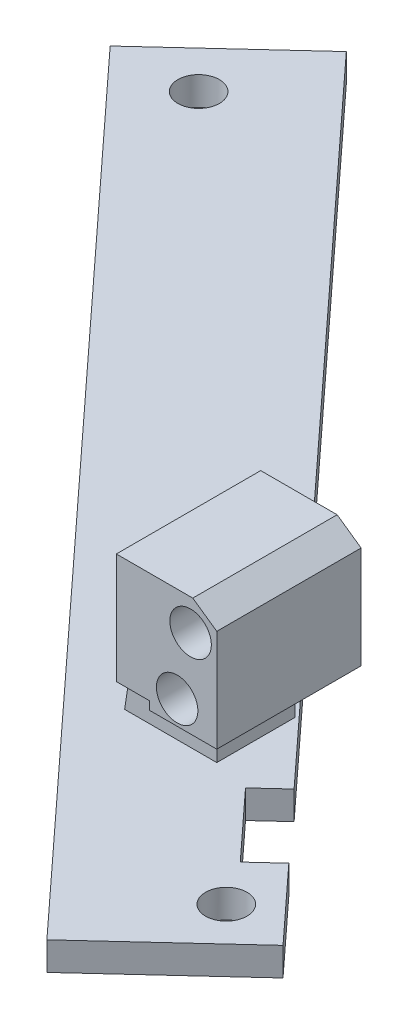
SolidWorks part; units mm, degrees
ref_plane "Front Plane" through (0, 0, 0) normal (0, 0, 1) x (1, 0, 0)
ref_plane "Top Plane" through (0, 0, 0) normal (0, 1, 0) x (1, 0, 0)
ref_plane "Right Plane" through (0, 0, 0) normal (1, 0, 0) x (0, 0, -1)
sketch "Sketch1" plane through (0, 0, 0) normal (0, 0, 1) x (1, 0, 0)
  line L0 (-629.0113, 228.5148) -> (-646.4173, 232.1744)
  line L1 (-625.5069, 227.7779) -> (-640.2031, 230.8679) construction
  line L2 (-646.4173, 232.1744) -> (-650.3578, 213.4325)
  line L3 (-650.3578, 213.4325) -> (-632.9518, 209.7729)
  line L4 (-626.0822, 208.3286) -> (-644.038, 212.1038) construction
  line L6 (-629.0113, 228.5148) -> (-629.0113, 209.7729)
  line L7 (-629.0113, 209.7729) -> (-632.9518, 209.7729)
  circle A0 centre (-635.0536, 225) radius 3.175
  circle A1 centre (-637.1112, 215.214) radius 3.175
  dimension "D4" = 6.35
  dimension "D5" = 6.35
  dimension "D1" = 6.35
  dimension "D2" = 19.1516
  dimension "D3" = 18.7418
  dimension "D6" = 21.3464
extrude "Boss-Extrude1" add sketch "Sketch1" along normal up to surface (22.098 mm away)
sketch "Sketch2" plane through (15.4424, 73.4471, 0) normal (-0.2058, -0.9786, 0) x (0.9786, -0.2058, 0)
  line L0 (-680.3571, 22.098) -> (-680.3571, 0)
  line L1 (-680.3571, 0) -> (-673.9925, 0)
  line L2 (-680.3571, 0) -> (-662.5706, 0) construction
  line L3 (-673.9925, 0) -> (-673.9925, 22.098)
  line L4 (-662.5706, 22.098) -> (-680.3571, 22.098) construction
  line L5 (-673.9925, 22.098) -> (-680.3571, 22.098)
  dimension "D1" = 6.3646
extrude "Boss-Extrude2" add sketch "Sketch2" along normal blind 8.89 contours L5 L0 L1 L3
ref_plane "Plane5" through (0, 204.7328, 0) normal (0, 1, 0) x (1, 0, 0)
sketch "Sketch12" plane through (0, 204.7328, 0) normal (0, 1, 0) x (1, 0, 0)
  line L11 (-739.2843, 69.8218) -> (-720.4707, 87.1577)
  line L12 (-720.4707, 87.1577) -> (-606.8199, -36.1806)
  line L13 (-606.8199, -36.1806) -> (-625.6335, -53.5165)
  line L14 (-625.6335, -53.5165) -> (-739.2843, 69.8218)
  circle A0 centre (-616.6175, -35.0666) radius 3.175
  circle A1 centre (-726.4769, 70.5586) radius 3.175
  dimension "D1" = 6.35
  dimension "D2" = 6.35
extrude "Boss-Extrude6" add sketch "Sketch12" against normal up to surface (4.3268 mm away)
sketch "Sketch21" plane through (0, 0, 0) normal (0, 0, -1) x (-1, 0, 0)
  line L0 (644.1294, 212.123) -> (644.1294, 204.7328)
  line L1 (419.4444, 204.7328) -> (-419.4444, 204.7328) construction
  line L2 (644.1294, 204.7328) -> (645.6832, 204.7328)
  line L3 (645.6832, 204.7328) -> (644.1294, 212.123) construction
  line L4 (645.6832, 204.7328) -> (644.1294, 212.123)
extrude "Boss-Extrude13" add sketch "Sketch21" against normal blind 22.098
sketch "Sketch22" plane through (0, 204.7328, 0) normal (0, 1, 0) x (1, 0, 0)
  line L4 (-644.1294, 0) -> (-644.1294, -22.098)
  line L5 (-632.9518, 0) -> (-644.1294, 0)
  line L6 (-632.9518, -22.098) -> (-632.9518, 0)
  line L7 (-644.1294, -22.098) -> (-632.9518, -22.098)
  line L8 (-644.1294, 0) -> (-644.1294, -22.098)
  line L9 (-632.9518, 0) -> (-644.1294, 0)
  line L11 (-644.1294, -22.098) -> (-632.9518, -22.098)
  line L12 (-632.9518, -22.098) -> (-632.9518, 0)
  dimension "D1" = 0
extrude "Boss-Extrude14" add sketch "Sketch22" along normal up to body
sketch "Sketch24" plane through (0, 204.7328, 0) normal (0, 1, 0) x (1, 0, 0)
  line L0 (-626.6984, -14.6077) -> (-630.5687, -18.1741)
  line L1 (-606.8199, -36.1806) -> (-632.9518, -7.8212) construction
  line L2 (-630.5687, -18.1741) -> (-621.1387, -28.4079)
  line L3 (-621.1387, -28.4079) -> (-617.2683, -24.8416)
  line L4 (-617.2683, -24.8416) -> (-626.6984, -14.6077)
  line L5 (-625.6335, -53.5165) -> (-606.8199, -36.1806) construction
  line L6 (-739.2843, 69.8218) -> (-625.6335, -53.5165) construction
  dimension "D1" = 13.9161
  dimension "D2" = 15.4189
  dimension "D3" = 20.32
extrude "Cut-Extrude4" cut sketch "Sketch24" against normal blind 10.922
sketch "Sketch30" plane through (0, 0, 22.098) normal (0, 0, 1) x (1, 0, 0)
  line L0 (-646.4173, 232.1744) -> (-646.4173, 204.7328)
  line L1 (-632.9518, 204.7328) -> (-652.1869, 204.7328) construction
  line L2 (-646.4173, 204.7328) -> (-652.1869, 204.7328)
  line L3 (-652.1869, 204.7328) -> (-646.4173, 232.1744)
extrude "Cut-Extrude6" cut sketch "Sketch30" against normal blind 69.342
sketch "Sketch32" plane through (0, 0, 22.098) normal (0, 0, 1) x (1, 0, 0)
  line L0 (-629.0113, 228.5148) -> (-646.4173, 228.5148)
  line L1 (-646.4173, 204.7328) -> (-646.4173, 232.1744) construction
  line L2 (-646.4173, 228.5148) -> (-646.4173, 232.1744)
  line L3 (-646.4173, 232.1744) -> (-629.0113, 228.5148)
extrude "Cut-Extrude7" cut sketch "Sketch32" against normal blind 69.342
sketch "Sketch33" plane through (0, 228.5148, 0) normal (0, 1, 0) x (1, 0, 0)
  line L1 (-646.4173, 0) -> (-629.0113, 0)
  line L2 (-646.4173, 0) -> (-646.4173, -22.098)
  line L3 (-646.4173, -22.098) -> (-629.0113, -22.098)
  line L4 (-629.0113, 0) -> (-629.0113, -22.098)
extrude "Boss-Extrude17" add sketch "Sketch33" along normal blind 1.27
sketch "Sketch34" plane through (0, 0, 22.098) normal (0, 0, 1) x (1, 0, 0)
  line L0 (-646.4173, 229.7848) -> (-629.0113, 229.7848) construction
  line L1 (-631.0433, 229.7848) -> (-629.0113, 229.7848)
  line L2 (-631.0433, 229.7848) -> (-631.0433, 209.7729)
  line L3 (-631.0433, 209.7729) -> (-629.0113, 209.7729)
  line L4 (-629.0113, 229.7848) -> (-629.0113, 209.7729)
  dimension "D1" = 2.032
extrude "Cut-Extrude8" cut sketch "Sketch34" against normal blind 40.132
sketch "Sketch35" plane through (0, 0, 22.098) normal (0, 0, 1) x (1, 0, 0)
  line L0 (-634.7139, 229.7848) -> (-631.0433, 227.2146)
  line L1 (-646.4173, 229.7848) -> (-631.0433, 229.7848) construction
  line L2 (-631.0433, 229.7848) -> (-631.0433, 209.7729) construction
  line L3 (-631.0433, 227.2146) -> (-631.0433, 229.7848)
  line L4 (-631.0433, 229.7848) -> (-634.7139, 229.7848)
  dimension "D1" = 55
  dimension "D2" = 4.481
extrude "Cut-Extrude9" cut sketch "Sketch35" against normal blind 40.132
sketch "Sketch36" plane through (-646.4173, 0, 0) normal (-1, 0, 0) x (0, 0, 1)
  line L1 (0, 204.7328) -> (5.08, 204.7328)
  line L2 (0, 204.7328) -> (0, 211.5908)
  line L3 (0, 211.5908) -> (5.08, 211.5908)
  line L4 (5.08, 204.7328) -> (5.08, 211.5908)
  line L5 (22.098, 204.7328) -> (17.018, 204.7328)
  line L6 (22.098, 204.7328) -> (22.098, 211.5908)
  line L7 (22.098, 211.5908) -> (17.018, 211.5908)
  line L8 (17.018, 204.7328) -> (17.018, 211.5908)
  dimension "D1" = 5.08
  dimension "D2" = 6.858
  dimension "D3" = 6.858
  dimension "D4" = 5.08
extrude "Cut-Extrude10" cut sketch "Sketch36" against normal blind 19.812
sketch "Sketch38" plane through (-631.0433, 0, 0) normal (1, 0, 0) x (0, 0, -1)
  line L0 (419.4444, 204.7328) -> (-419.4444, 204.7328) construction
  line L1 (-17.018, 211.5908) -> (-5.08, 211.5908)
  line L2 (-17.018, 211.5908) -> (-17.018, 204.7328)
  line L3 (-17.018, 204.7328) -> (-5.08, 204.7328)
  line L4 (-5.08, 211.5908) -> (-5.08, 204.7328)
  line L5 (-5.08, 204.7328) -> (-5.08, 209.7729) construction
extrude "Cut-Extrude11" cut sketch "Sketch38" against normal blind 5.08
sketch "Sketch39" plane through (-646.4173, 0, 0) normal (-1, 0, 0) x (0, 0, 1)
  line L0 (0, 211.5908) -> (0, 212.8608)
  line L1 (0, 229.7848) -> (0, 211.5908) construction
  line L2 (0, 212.8608) -> (1.27, 211.5908)
  line L3 (5.08, 211.5908) -> (0, 211.5908) construction
  line L4 (1.27, 211.5908) -> (0, 211.5908)
  line L5 (22.098, 211.5908) -> (22.098, 212.8608)
  line L6 (22.098, 211.5908) -> (22.098, 229.7848) construction
  line L7 (22.098, 212.8608) -> (20.828, 211.5908)
  line L8 (22.098, 211.5908) -> (17.018, 211.5908) construction
  line L9 (20.828, 211.5908) -> (22.098, 211.5908)
  dimension "D1" = 1.27
  dimension "D2" = 1.27
  dimension "D3" = 1.27
extrude "Cut-Extrude12" cut sketch "Sketch39" against normal blind 5.08
ref_plane "Plane6" through (0, 0, 11.049) normal (0, 0, 1) x (1, 0, 0)
sketch "Sketch41" plane through (0, 0, 11.049) normal (0, 0, 1) x (1, 0, 0)
  line L0 (-646.4173, 229.7848) -> (-646.4173, 204.7328)
  line L1 (419.4444, 204.7328) -> (-419.4444, 204.7328) construction
  line L2 (-646.4173, 204.7328) -> (-650.2273, 204.7328)
  line L3 (-739.2843, 204.7328) -> (-625.6335, 204.7328) construction
  line L4 (-650.2273, 204.7328) -> (-646.4173, 229.7848)
  dimension "D1" = 3.81
extrude "Boss-Extrude18" add sketch "Sketch41" along normal up to surface and the other way up to surface up to face at (-641.2703, 208.1618, 17.018) other way up to face at (-641.2703, 208.1618, 5.08)
